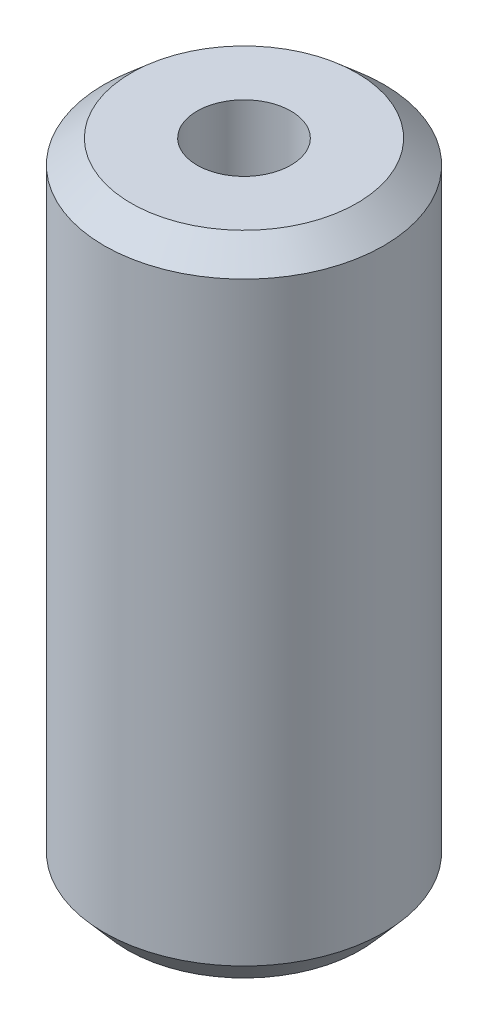
SolidWorks part; units mm, degrees
ref_plane "Front Plane" through (0, 0, 0) normal (0, 0, 1) x (1, 0, 0)
ref_plane "Top Plane" through (0, 0, 0) normal (0, 1, 0) x (1, 0, 0)
ref_plane "Right Plane" through (0, 0, 0) normal (1, 0, 0) x (0, 0, -1)
sketch "Sketch1" plane through (0, 0, 0) normal (0, 1, 0) x (1, 0, 0)
  circle A0 centre (0, 0) radius 22.5
  dimension "SHAFT_OD" = 45
extrude "Boss-Extrude1" add sketch "Sketch1" along normal blind 103.8606
sketch "Sketch2" plane through (0, 0, 0) normal (0, 1, 0) x (1, 0, 0)
  circle A0 centre (0, 0) radius 7.5577
  dimension "BORE_D" = 15.1154
extrude "Cut-Extrude1" cut sketch "Sketch2" along normal through all
chamfer "Chamfer1" distance 3.7591 angle 48.995 2 edges at (0, 103.8606, 22.5) (0, 0, 22.5) first distance on face at (0, 103.8606, 22.5) first distance on face at (0, 0, 7.5577)
